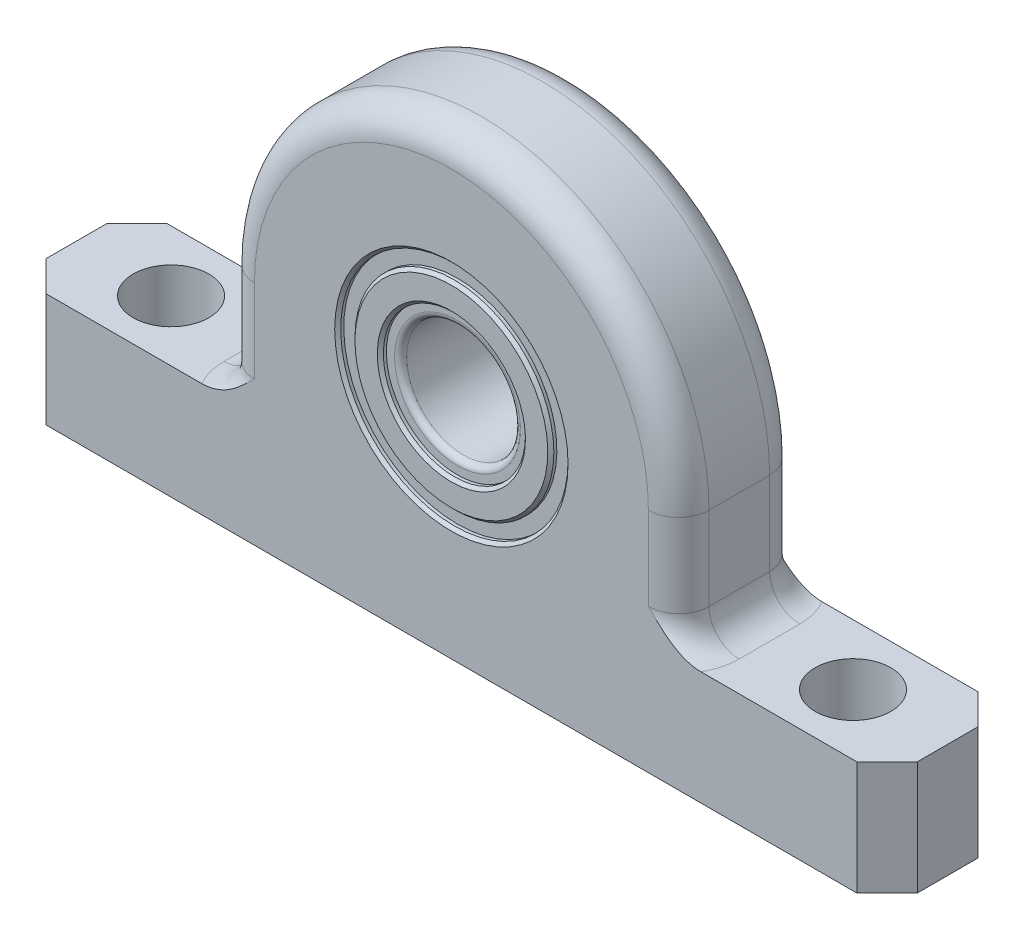
SolidWorks part; units mm, degrees
ref_plane "Front Plane" through (0, 0, 0) normal (0, 0, 1) x (1, 0, 0)
ref_plane "Top Plane" through (0, 0, 0) normal (0, 1, 0) x (1, 0, 0)
ref_plane "Right Plane" through (0, 0, 0) normal (1, 0, 0) x (0, 0, -1)
sketch "Sketch1" plane through (0, 0, 0) normal (0, 0, 1) x (1, 0, 0)
  line L0 (9.525, 0) -> (9.525, -4.7625)
  line L1 (9.525, -4.7625) -> (18.2562, -4.7625)
  line L2 (18.2562, -4.7625) -> (18.2562, -9.525)
  line L3 (18.2562, -9.525) -> (-18.2562, -9.525)
  line L4 (-18.2562, -9.525) -> (-18.2563, -4.7625)
  line L5 (-18.2563, -4.7625) -> (-9.525, -4.7625)
  line L6 (-9.525, -4.7625) -> (-9.525, 0)
  circle A0 centre (0, 0) radius 2.3813
  arc A1 (9.525, 0) -> (-9.525, 0) centre (0, 0) ccw
  circle A2 centre (0, 0) radius 4.7625
  dimension "D1" = 9.525
sketch "Sketch2" plane through (0, 0, 0) normal (0, 1, 0) x (1, 0, 0)
  line L0 (0, 2.54) -> (0, -2.54) construction
  line L1 (-14.2875, 0) -> (14.2875, 0) construction
  circle A0 centre (14.2875, 0) radius 1.5875
  circle A1 centre (-14.2875, 0) radius 1.5875
sketch "Sketch3" plane through (0, 0, 0) normal (0, 0, 1) x (1, 0, 0)
  line L0 (9.525, 0) -> (9.525, -4.7625) construction
  line L1 (18.2562, -4.7625) -> (18.2562, -9.525) construction
  line L2 (9.525, -4.7625) -> (18.2562, -4.7625) construction
  line L3 (18.2562, -9.525) -> (-18.2562, -9.525) construction
  line L4 (-18.2562, -9.525) -> (-18.2563, -4.7625) construction
  line L5 (-18.2563, -4.7625) -> (-9.525, -4.7625) construction
  line L6 (-9.525, -4.7625) -> (-9.525, 0) construction
  line L7 (9.525, 0) -> (9.525, -4.7625)
  line L8 (18.2562, -4.7625) -> (18.2562, -9.525)
  line L9 (9.525, -4.7625) -> (18.2562, -4.7625)
  line L10 (18.2562, -9.525) -> (-18.2562, -9.525)
  line L11 (-18.2562, -9.525) -> (-18.2563, -4.7625)
  line L12 (-18.2563, -4.7625) -> (-9.525, -4.7625)
  line L13 (-9.525, -4.7625) -> (-9.525, 0)
  arc A0 (9.525, 0) -> (-9.525, 0) centre (0, 0) ccw construction
  circle A1 centre (0, 0) radius 4.7625 construction
  arc A2 (9.525, 0) -> (-9.525, 0) centre (0, 0) ccw
  circle A3 centre (0, 0) radius 4.7625
extrude "Extrude1" add sketch "Sketch3" along normal up to vertex (2.54 mm away) and the other way up to vertex (2.54 mm away) up to point (0, 0, 2.54) other way up to point (0, 0, -2.54)
sketch "Sketch4" plane through (0, -4.7625, 0) normal (0, 1, 0) x (1, 0, 0)
  line L0 (-18.2563, 2.54) -> (-18.2562, 1.27)
  line L1 (-18.2563, -2.54) -> (-18.2563, 2.54) construction
  line L2 (-18.2562, 1.27) -> (-16.9863, 2.54)
  line L3 (-9.525, 2.54) -> (-18.2563, 2.54) construction
  line L4 (-16.9863, 2.54) -> (-18.2563, 2.54)
  line L5 (0, 0) -> (0, 2.54) construction
  line L6 (0, 0) -> (-14.2875, 0) construction
  line L7 (16.9863, 2.54) -> (18.2563, 2.54)
  line L8 (18.2562, 1.27) -> (16.9863, 2.54)
  line L9 (18.2563, 2.54) -> (18.2562, 1.27)
  line L10 (18.2563, -2.54) -> (18.2562, -1.27)
  line L11 (18.2562, -1.27) -> (16.9863, -2.54)
  line L12 (16.9863, -2.54) -> (18.2563, -2.54)
  line L13 (-16.9863, -2.54) -> (-18.2563, -2.54)
  line L14 (-18.2562, -1.27) -> (-16.9863, -2.54)
  line L15 (-18.2563, -2.54) -> (-18.2562, -1.27)
  circle A0 centre (-14.2875, 0) radius 1.5875 construction
  circle A1 centre (14.2875, 0) radius 1.5875 construction
  circle A2 centre (-14.2875, 0) radius 1.5875
  circle A3 centre (14.2875, 0) radius 1.5875
  dimension "D1" = 45
  dimension "D2" = 1.27
extrude "Cut-Extrude1" cut sketch "Sketch4" against normal through all
fillet "Fillet1" radius 1.27 6 edges at (9.525, -2.3812, -2.54) (-9.525, -2.3812, -2.54) (9.525, -2.3812, 2.54) (-9.525, -2.3812, 2.54) (0, 9.525, -2.54) (0, 9.525, 2.54)
fillet "Fillet2" radius 1.27 6 edges at (-9.153, -4.7625, 2.168) (-9.153, -4.7625, -2.168) (9.153, -4.7625, 2.168) (9.153, -4.7625, -2.168) (-9.525, -4.7625, 0) (9.525, -4.7625, 0)
chamfer "Chamfer1" distance 0.127 angle 45 2 edges at (4.7625, 0, -2.54) (4.7625, 0, 2.54)
sketch "Sketch5" plane through (0, 0, 0) normal (1, 0, 0) x (0, 0, -1)
  line L0 (0, 0) -> (0, 4.7625) construction
  line L1 (0, 4.7625) -> (0, -4.7625) construction
  line L2 (0, 2.3813) -> (0, -2.3813) construction
  line L3 (-2.286, 4.7625) -> (-2.286, 4.1672)
  line L4 (-2.286, 4.1672) -> (-2.54, 4.1672)
  line L5 (-2.54, 4.1672) -> (-2.54, 2.9766)
  line L6 (-2.54, 2.9766) -> (-2.286, 2.9766)
  line L7 (-2.286, 2.9766) -> (-2.286, 2.3812)
  line L8 (-2.286, 2.3812) -> (2.286, 2.3812)
  line L9 (0, 2.3813) -> (0, 4.7625) construction
  line L10 (-2.286, 4.7625) -> (2.286, 4.7625)
  line L11 (-2.54, 8.255) -> (-2.54, 0) construction
  line L12 (2.286, 2.9766) -> (2.286, 2.3812)
  line L13 (2.54, 2.9766) -> (2.286, 2.9766)
  line L14 (2.54, 4.1672) -> (2.54, 2.9766)
  line L15 (2.286, 4.1672) -> (2.54, 4.1672)
  line L16 (2.286, 4.7625) -> (2.286, 4.1672)
  line L17 (0, 0) -> (-2.54, 0) construction
  point P6 (0, 2.3812)
  dimension "D2" = 2.3812
  dimension "D3" = 1.1906
revolve "Revolve1" add sketch "Sketch5" angle 360 about L17
fillet "Fillet3" radius 0.254 2 edges at (0, 2.3812, 2.286) (0, 2.3812, -2.286)
chamfer "Chamfer2" distance 0.127 angle 45 4 edges at (0, 2.9766, -2.54) (0, 4.1672, -2.54) (0, 4.1672, 2.54) (0, 2.9766, 2.54)
equation "\"D1@Sketch1\" = \"shaft dia@Sketch1\"*2."
equation "\"D2@Sketch4\" = \"E@Sketch2\"/4"
equation "\"D1@Fillet1\" = \"D2@Sketch4\""
equation "\"D1@Fillet2\" = \"D1@Fillet1\""
equation "\"D3@Sketch5\" = \"D2@Sketch5\"/2"
